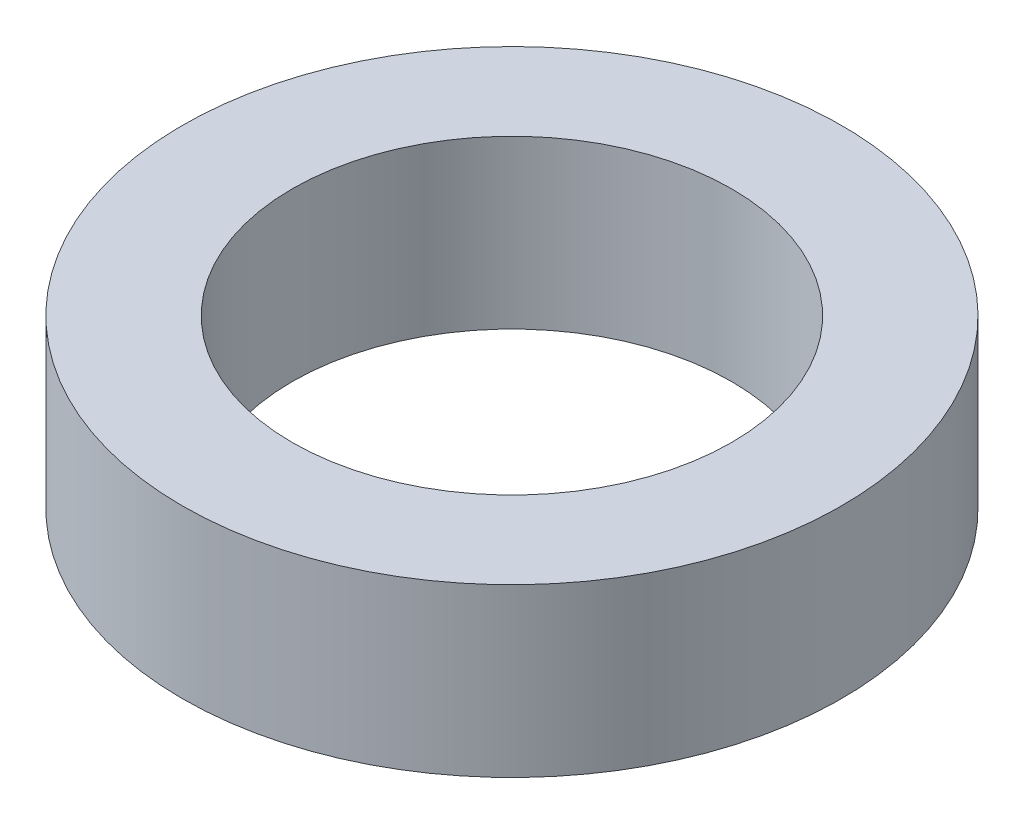
SolidWorks part; units mm, degrees
ref_plane "Front Plane" through (0, 0, 0) normal (0, 0, 1) x (1, 0, 0)
ref_plane "Top Plane" through (0, 0, 0) normal (0, 1, 0) x (1, 0, 0)
ref_plane "Right Plane" through (0, 0, 0) normal (1, 0, 0) x (0, 0, -1)
sketch "Sketch1" plane through (0, 0, 0) normal (0, 1, 0) x (1, 0, 0)
  circle A0 centre (0, 0) radius 37.5
  dimension "FLANGE_OD" = 75
extrude "Boss-Extrude1" add sketch "Sketch1" along normal blind 19
sketch "Sketch2" plane through (0, 0, 0) normal (0, 1, 0) x (1, 0, 0)
  circle A0 centre (0, 0) radius 25
  dimension "BORE_D" = 50
extrude "Cut-Extrude1" cut sketch "Sketch2" along normal through all
sketch "Sketch3" plane through (0, 19, 0) normal (0, 1, 0) x (1, 0, 0)
  circle A0 centre (0, 0) radius 16.3331 construction
  circle A1 centre (-16.3331, 0) radius 2.0962
  dimension "BOLT_D" = 4.1924
  dimension "BOLT_PCD" = 32.6661
extrude "Cut-Extrude2" cut sketch "Sketch3" against normal blind 16.0843 rebuild error yes
pattern_circular "CirPattern1" count 6 over 360 rebuild error yes
